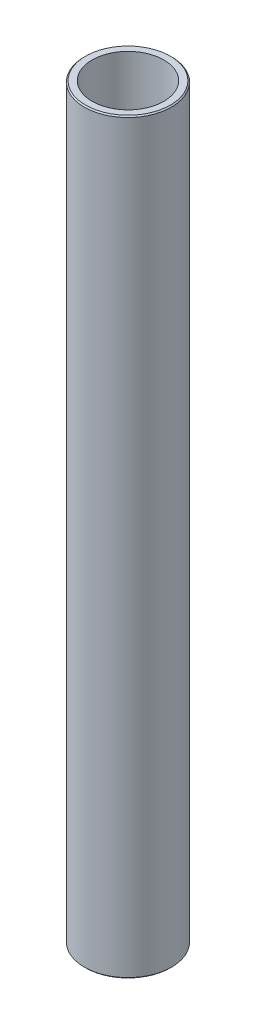
SolidWorks part; units mm, degrees
ref_plane "Front Plane" through (0, 0, 0) normal (0, 0, 1) x (1, 0, 0)
ref_plane "Top Plane" through (0, 0, 0) normal (0, 1, 0) x (1, 0, 0)
ref_plane "Right Plane" through (0, 0, 0) normal (1, 0, 0) x (0, 0, -1)
sketch "Sketch1" plane through (0, 0, 0) normal (0, 1, 0) x (1, 0, 0)
  circle A0 centre (0, 0) radius 35
  dimension "SHAFT_OD" = 70
extrude "Boss-Extrude1" add sketch "Sketch1" along normal blind 600
sketch "Sketch2" plane through (0, 0, 0) normal (0, 1, 0) x (1, 0, 0)
  circle A0 centre (0, 0) radius 28.8109
  dimension "BORE_D" = 57.6218
extrude "Cut-Extrude1" cut sketch "Sketch2" along normal through all
chamfer "Chamfer1" distance 0.9536 angle 45 2 edges at (0, 600, 35) (0, 0, 35)
